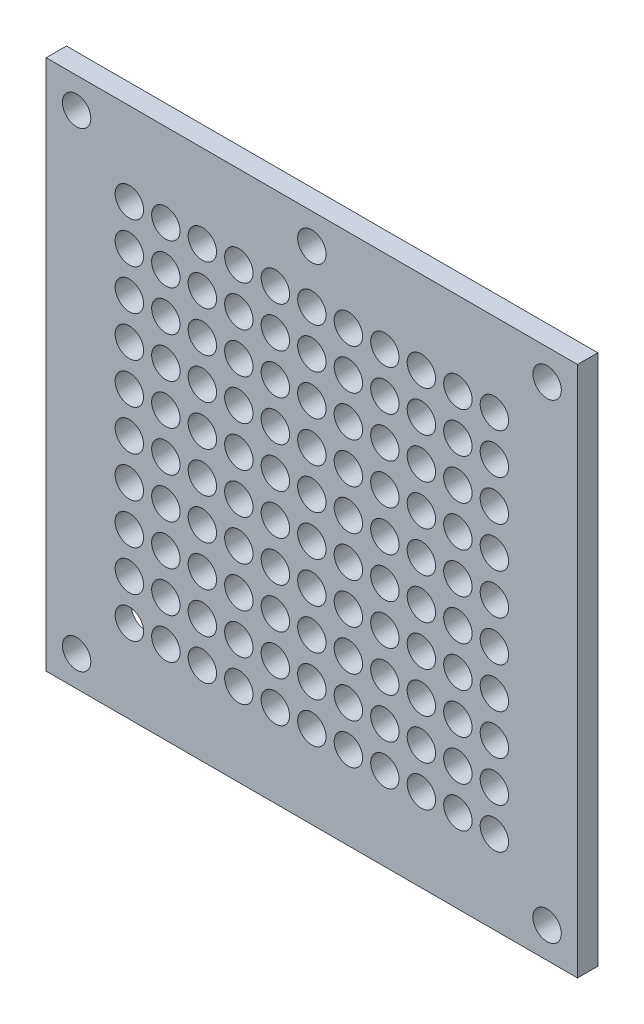
SolidWorks part; units mm, degrees
ref_plane "Ebene vorne" through (0, 0, 0) normal (0, 0, 1) x (1, 0, 0)
ref_plane "Ebene oben" through (0, 0, 0) normal (0, 1, 0) x (1, 0, 0)
ref_plane "Ebene rechts" through (0, 0, 0) normal (1, 0, 0) x (0, 0, -1)
sketch "Skizze2" plane through (0, 0, 0) normal (0, 0, 1) x (1, 0, 0)
  line L0 (-65.5, 65.5) -> (-65.5, -65.5) construction
  line L1 (-65.5, -65.5) -> (65.5, -65.5) construction
  line L2 (65.5, 65.5) -> (-65.5, 65.5) construction
  line L3 (65.5, -65.5) -> (65.5, 65.5) construction
  line L4 (-65.5, 65.5) -> (-65.5, -65.5)
  line L5 (-65.5, -65.5) -> (65.5, -65.5)
  line L6 (65.5, 65.5) -> (-65.5, 65.5)
  line L7 (65.5, -65.5) -> (65.5, 65.5)
extrude "Aufsatz-Linear austragen1" add sketch "Skizze2" along normal blind 5
sketch "Skizze3" plane through (0, 0, 0) normal (0, 0, -1) x (-1, 0, 0)
  line L0 (0, 65.5) -> (0, 0) construction
  line L1 (-65.5, 65.5) -> (65.5, 65.5) construction
  line L2 (-67.5, 67.5) -> (67.5, 67.5) construction
  circle A0 centre (0, 58) radius 3.5
  dimension "D1" = 7
  dimension "D2" = 9.5
extrude "Schnitt-Linear austragen1" cut sketch "Skizze3" against normal up to surface (5 mm away) up to face at (0, 0, 5)
sketch "Skizze4" plane through (0, 0, 0) normal (0, 0, -1) x (-1, 0, 0)
  line L0 (0, 0) -> (0, 65.5) construction
  line L1 (-65.5, 65.5) -> (65.5, 65.5) construction
  line L2 (-67.5, 67.5) -> (67.5, 67.5) construction
  circle A0 centre (0, 45) radius 3.5
  dimension "D1" = 7
  dimension "D2" = 22.5
extrude "Schnitt-Linear austragen2" cut sketch "Skizze4" against normal up to surface (5 mm away) up to face at (3.5, 58, 5)
pattern_linear "Lineares Muster1" count 6 spacing 9 along (1, 0, 0) count 10 spacing 10 along (0, -1, 0) of "Schnitt-Linear austragen2"
pattern_linear "Lineares Muster2" count 6 spacing 9 along (-1, 0, 0) count 10 spacing 10 along (0, -1, 0) skipping (0, 1), (0, 2), (0, 3), (0, 4), (0, 5), (0, 6), (0, 7), (0, 8), (0, 9) of "Schnitt-Linear austragen2"
sketch "Skizze5" plane through (0, 0, 0) normal (0, 0, -1) x (-1, 0, 0)
  line L0 (-67.5, -67.5) -> (-67.5, 67.5) construction
  line L1 (-67.5, 67.5) -> (67.5, 67.5) construction
  line L2 (67.5, 67.5) -> (67.5, -67.5) construction
  line L3 (67.5, -67.5) -> (-67.5, -67.5) construction
  circle A0 centre (-50, 50) radius 5.5
  circle A1 centre (50, 50) radius 5.5
  circle A2 centre (-50, -50) radius 5.5
  circle A3 centre (50, -50) radius 5.5
  dimension "D1" = 11
  dimension "D3" = 17.5
  dimension "D4" = 11
  dimension "D5" = 17.5
  dimension "D6" = 17.5
  dimension "D7" = 11
  dimension "D8" = 11
  dimension "D9" = 17.5
  dimension "D10" = 17.5
  dimension "D11" = 17.5
  dimension "D12" = 17.5
  dimension "D2" = 17.5
extrude "Schnitt-Linear austragen3" cut sketch "Skizze5" against normal blind 1
sketch "Skizze6" plane through (0, 0, 0) normal (0, 0, -1) x (-1, 0, 0)
  line L0 (-67.5, -67.5) -> (-67.5, 67.5) construction
  line L1 (-67.5, 67.5) -> (67.5, 67.5) construction
  line L2 (67.5, -67.5) -> (-67.5, -67.5) construction
  line L3 (67.5, 67.5) -> (67.5, -67.5) construction
  circle A0 centre (-58, 58) radius 3.5
  circle A1 centre (-58, -58) radius 3.5
  circle A2 centre (58, -58) radius 3.5
  circle A3 centre (58, 58) radius 3.5
  dimension "D1" = 7
  dimension "D2" = 9.5
  dimension "D3" = 9.5
  dimension "D4" = 7
  dimension "D5" = 7
  dimension "D6" = 7
  dimension "D7" = 9.5
  dimension "D8" = 9.5
  dimension "D9" = 9.5
  dimension "D11" = 9.5
  dimension "D12" = 9.5
  dimension "D10" = 9.5
extrude "Schnitt-Linear austragen4" cut sketch "Skizze6" against normal up to surface (5 mm away) up to face at (-41.5, -45, 5)
sketch "Skizze7" plane through (0, 0, 1) normal (0, 0, -1) x (-1, 0, 0)
  circle A0 centre (-50, 50) radius 3
  circle A1 centre (50, 50) radius 3
  circle A2 centre (50, -50) radius 3
  circle A3 centre (-50, -50) radius 3
extrude "Schnitt-Linear austragen5" cut sketch "Skizze7" against normal blind 1.2
